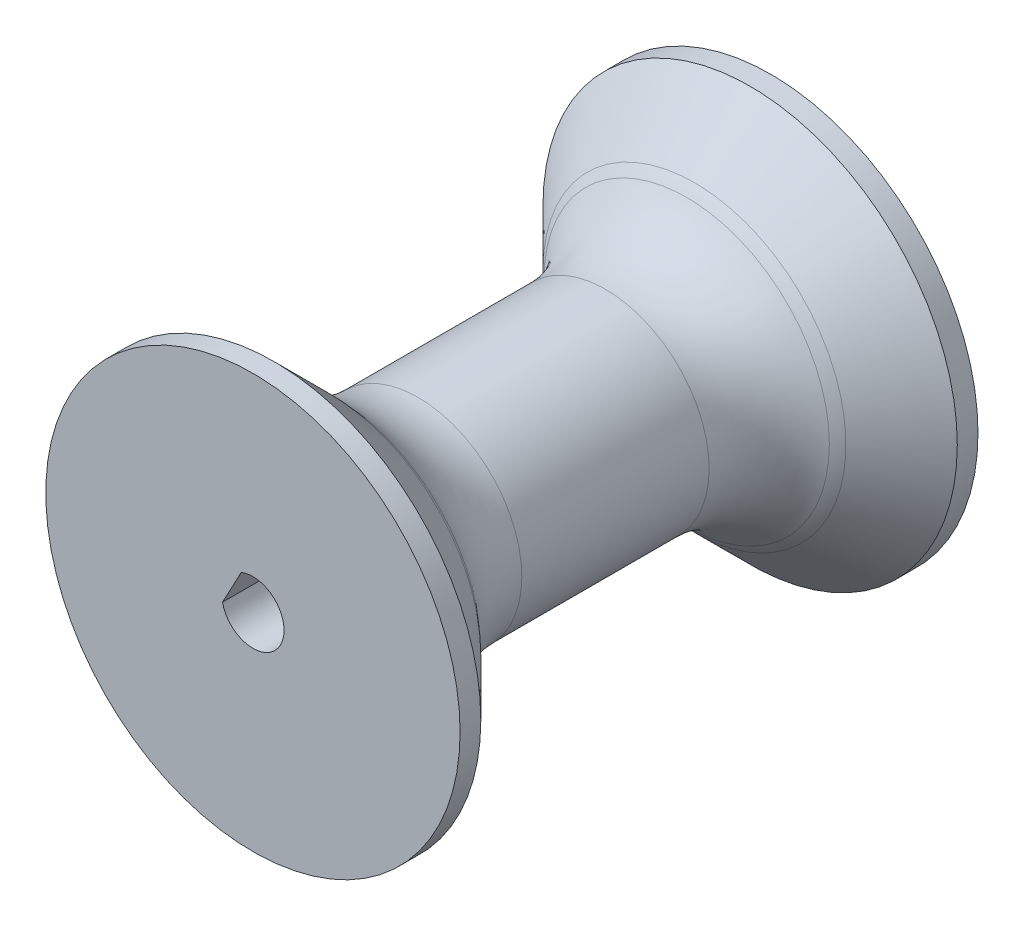
SolidWorks part; units mm, degrees
ref_plane "Front Plane" through (0, 0, 0) normal (0, 0, 1) x (1, 0, 0)
ref_plane "Top Plane" through (0, 0, 0) normal (0, 1, 0) x (1, 0, 0)
ref_plane "Right Plane" through (0, 0, 0) normal (1, 0, 0) x (0, 0, -1)
sketch "Sketch1" plane through (0, 0, 0) normal (0, 0, 1) x (1, 0, 0)
  circle A0 centre (0, 0) radius 10
  dimension "D1" = 20
extrude "Boss-Extrude1" add sketch "Sketch1" along normal blind 5 contours A0
sketch "Sketch3" plane through (0, 0, 5) normal (0, 0, 1) x (1, 0, 0)
  circle A0 centre (0, 0) radius 5
  dimension "D1" = 10
extrude "Boss-Extrude3" add sketch "Sketch3" along normal blind 15
sketch "Sketch4" plane through (0, 0, 20) normal (0, 0, 1) x (1, 0, 0)
  circle A1 centre (0, 0) radius 10
extrude "Boss-Extrude4" add sketch "Sketch4" along normal blind 5
sketch "Sketch5" plane through (0, 0, 0) normal (0, 0, -1) x (-1, 0, 0)
  line L2 (0.5672, 1.3886) -> (1.4688, -0.3042)
  arc A0 (0.5672, 1.3886) -> (1.4688, -0.3042) centre (0, 0) ccw
extrude "Cut-Extrude1" cut sketch "Sketch5" against normal blind 26
chamfer "Chamfer3" distance 4 angle 45 2 edges at (10, 0, 20) (10, 0, 5)
fillet "Fillet6" radius 5 2 edges at (6, 0, 20) (6, 0, 5)
fillet "Fillet7" radius 5 2 edges at (5, 0, 20) (5, 0, 5)
